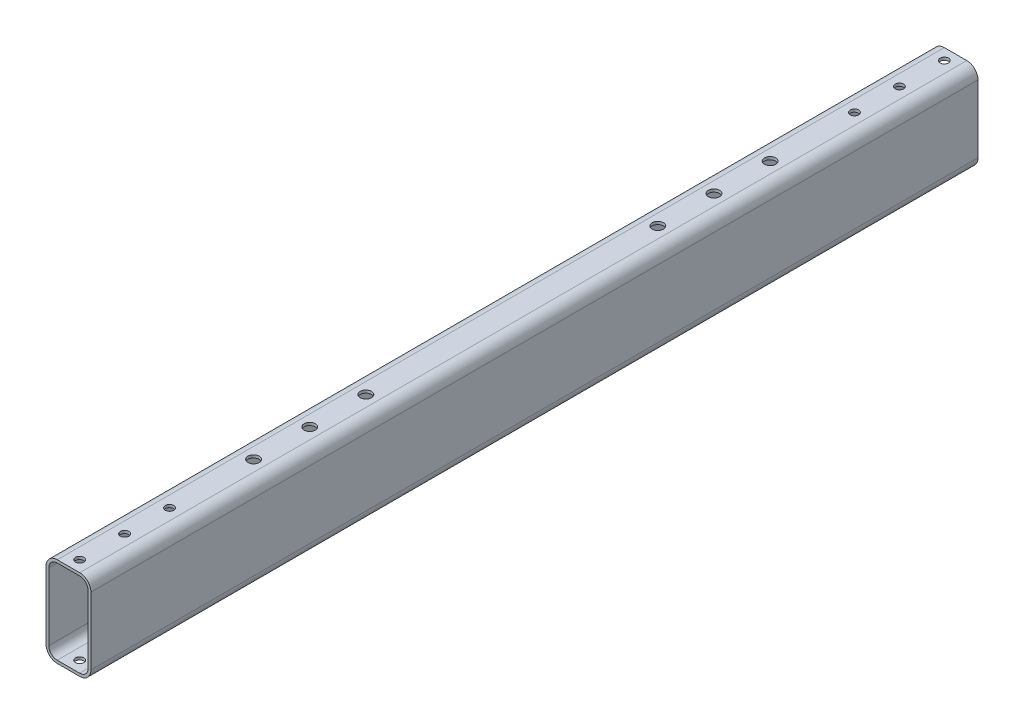
SolidWorks part; units mm, degrees
material "6061-T6 (SS)"
ref_plane "Front Plane" through (0, 0, 0) normal (0, 0, 1) x (1, 0, 0)
ref_plane "Top Plane" through (0, 0, 0) normal (0, 1, 0) x (1, 0, 0)
ref_plane "Right Plane" through (0, 0, 0) normal (1, 0, 0) x (0, 0, -1)
sketch "Sketch1" plane through (0, 0, 0) normal (0, 0, 1) x (1, 0, 0)
  line L1 (-6.35, -25.4) -> (6.35, -25.4)
  line L2 (-12.7, -19.05) -> (-12.7, 19.05)
  line L3 (-6.35, 25.4) -> (6.35, 25.4)
  line L4 (12.7, -19.05) -> (12.7, 19.05)
  line L5 (-12.7, -25.4) -> (12.7, 25.4) construction
  line L6 (-12.7, 25.4) -> (12.7, -25.4) construction
  arc A0 (-12.7, -19.05) -> (-6.35, -25.4) centre (-6.35, -19.05) ccw
  arc A1 (6.35, -25.4) -> (12.7, -19.05) centre (6.35, -19.05) ccw
  arc A2 (6.35, 25.4) -> (12.7, 19.05) centre (6.35, 19.05) cw
  arc A3 (-12.7, 19.05) -> (-6.35, 25.4) centre (-6.35, 19.05) cw
  point P0 (0, 0)
  dimension "D3" = 6.35
  dimension "D1" = 50.8
  dimension "D2" = 25.4
extrude "Extrude-Thin1" add sketch "Sketch1" along normal blind 501.65 thin thin type one direction reverse wall 1.5875
hole_wizard "3/16 (0.1875) Diameter Hole1" positions "3DSketch1" profile "Sketch3" hole size "3/16" standard "ANSI Inch" end condition through all
sketch3d "3DSketch1"
  line L1 (6.35, 25.4, 0) -> (-6.35, 25.4, 0) construction
  line L6 (0, 25.4, 501.65) -> (0, 25.4, 0) construction
  line L7 (6.35, 25.4, 501.65) -> (-6.35, 25.4, 501.65) construction
  point P57 (0, 25.4, 6.35)
  point P59 (0, 25.4, 31.75)
  point P61 (0, 25.4, 57.15)
  point P63 (0, 25.4, 469.9)
  point P65 (0, 25.4, 444.5)
  point P67 (0, 25.4, 495.3)
  dimension "D1" = 25.4
  dimension "D2" = 25.4
  dimension "D3" = 6.35
  dimension "D4" = 25.4
  dimension "D5" = 25.4
  dimension "D6" = 6.35
sketch "Sketch3" plane through (0, 25.4, 495.3) normal (1, 0, 0) x (0, 0, 1)
  line L0 (0, 0) -> (0, 50.8)
  line L1 (0, 50.8) -> (2.3812, 50.8)
  line L2 (2.3812, 50.8) -> (2.3812, 0)
  line L5 (2.3812, 0) -> (0, 0)
  line L11 (0, -6.35) -> (0, 107.95) construction
  dimension "Thru Hole Dia." = 4.7625
  dimension "Thru Hole Depth" = 50.8
hole_wizard "3/16 (0.195) Diameter Hole1" positions "Sketch4" profile "Sketch5" hole size "3/16" standard "ANSI Inch" end condition up to next
sketch "Sketch4" plane through (0, -25.4, 0) normal (0, -1, 0) x (-1, 0, 0)
  point P28 (3.175, -85.725)
  point P31 (-3.175, -111.125)
  point P34 (3.175, -136.525)
  point P37 (-3.175, -161.925)
  point P40 (3.175, -187.325)
  point P43 (3.175, -339.725)
  point P46 (-3.175, -365.125)
  point P49 (3.175, -390.525)
  point P52 (-3.175, -415.925)
  point P60 (-3.175, -212.725)
  point P63 (3.175, -238.125)
  point P66 (-3.175, -263.525)
  point P69 (3.175, -288.925)
  point P72 (-3.175, -314.325)
sketch "Sketch5" plane through (-3.175, -25.4, 85.725) normal (1, 0, 0) x (0, 0, -1)
  line L0 (0, 0) -> (0, 1.5875)
  line L1 (0, 1.5875) -> (2.4765, 1.5875)
  line L2 (2.4765, 1.5875) -> (2.4765, 0)
  line L5 (2.4765, 0) -> (0, 0)
  line L11 (0, -6.35) -> (0, 107.95) construction
  dimension "Thru Hole Dia." = 4.953
  dimension "Thru Hole Depth" = 1.5875
hole_wizard "1/4 (0.25) Diameter Hole1" positions "Sketch7" profile "Sketch6" hole size "1/4" standard "ANSI Inch"
sketch "Sketch7" plane through (0, 25.4, 0) normal (0, 1, 0) x (1, 0, 0)
  point P0 (0, -104.85)
  point P3 (0, -136.6)
  point P6 (0, -168.35)
  point P9 (0, -396.9748)
  point P12 (0, -365.2248)
  point P15 (0, -333.4748)
sketch "Sketch6" plane through (0, 25.4, 104.85) normal (1, 0, 0) x (0, 0, 1)
  line L0 (0, 0) -> (0, 27.3077)
  line L1 (0, 27.3077) -> (3.175, 25.4)
  line L2 (3.175, 25.4) -> (3.175, 0)
  line L5 (3.175, 0) -> (0, 0)
  line L10 (0, 27.3077) -> (-3.175, 25.4) construction
  line L11 (0, -6.35) -> (0, 107.95) construction
  dimension "Hole Dia." = 6.35
  dimension "Hole Depth" = 25.4
  dimension "Drill Angle" = 118
